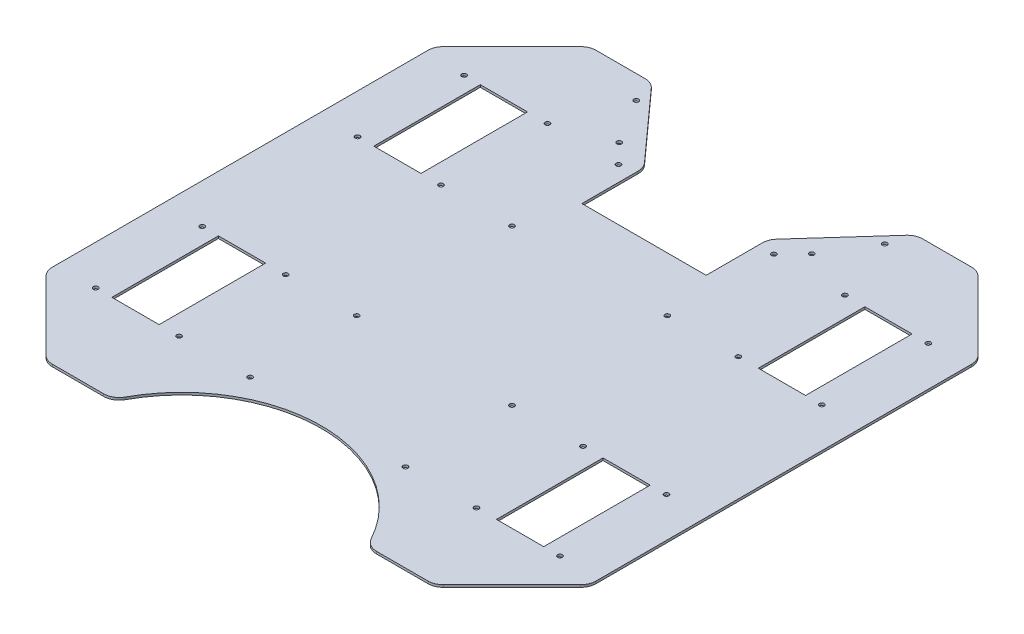
SolidWorks part; units mm, degrees
ref_plane "前视基准面" through (0, 0, 0) normal (0, 0, 1) x (1, 0, 0)
ref_plane "上视基准面" through (0, 0, 0) normal (0, 1, 0) x (1, 0, 0)
ref_plane "右视基准面" through (0, 0, 0) normal (1, 0, 0) x (0, 0, -1)
other "Configuration Table"
sketch "草图1" plane through (0, 0, 0) normal (0, 1, 0) x (1, 0, 0)
  line L0 (-125, 175) -> (-175, 125)
  line L1 (125, -175) -> (81.7103, -175)
  line L2 (175, -125) -> (175, 125)
  line L3 (125, 175) -> (85, 175)
  line L4 (-175, -125) -> (-175, 125)
  line L5 (-85, 175) -> (-40, 125)
  line L7 (125, 175) -> (175, 125)
  line L8 (175, -125) -> (125, -175)
  line L9 (-125, -175) -> (-175, -125)
  line L10 (40, 125) -> (85, 175)
  line L11 (-85, 175) -> (-125, 175)
  line L12 (40, 125) -> (40, 85)
  line L13 (40, 85) -> (-40, 85)
  line L14 (-40, 85) -> (-40, 125)
  line L15 (-138.994, 50) -> (-108.594, 50)
  line L16 (-108.594, 50) -> (-108.594, 118.58)
  line L17 (-108.594, 118.58) -> (-138.994, 118.58)
  line L18 (-138.994, 118.58) -> (-138.994, 50)
  line L19 (108.594, 50) -> (138.994, 50)
  line L20 (138.994, 50) -> (138.994, 118.58)
  line L21 (138.994, 118.58) -> (108.594, 118.58)
  line L22 (108.594, 118.58) -> (108.594, 50)
  line L23 (-175, 0) -> (175, 0) construction
  line L24 (-108.594, -118.58) -> (-138.994, -118.58)
  line L25 (-108.594, -50) -> (-108.594, -118.58)
  line L26 (-138.994, -50) -> (-108.594, -50)
  line L27 (-138.994, -118.58) -> (-138.994, -50)
  line L28 (138.994, -118.58) -> (108.594, -118.58)
  line L29 (138.994, -50) -> (138.994, -118.58)
  line L30 (108.594, -50) -> (138.994, -50)
  line L31 (108.594, -118.58) -> (108.594, -50)
  line L32 (-81.7103, -175) -> (-125, -175)
  line L33 (-80, 160) -> (-62, 131) construction
  circle A0 centre (-62, 131) radius 1.55
  circle A1 centre (-80, 160) radius 1.55
  circle A2 centre (62, 131) radius 1.55
  circle A3 centre (80, 160) radius 1.55
  circle A4 centre (-50, 118.58) radius 1.55
  circle A5 centre (-50, 50) radius 1.55
  circle A6 centre (-95.72, 50) radius 1.55
  circle A7 centre (-95.72, 118.58) radius 1.55
  circle A12 centre (-149.434, 118.58) radius 1.55
  circle A13 centre (-149.434, 50) radius 1.55
  circle A14 centre (-50, -118.58) radius 1.55
  circle A15 centre (-50, -50) radius 1.55
  circle A16 centre (-95.72, -50) radius 1.55
  circle A17 centre (-95.72, -118.58) radius 1.55
  circle A18 centre (-149.434, -50) radius 1.55
  circle A19 centre (-149.434, -118.58) radius 1.55
  circle A20 centre (50, 50) radius 1.55
  circle A21 centre (95.72, 50) radius 1.55
  circle A22 centre (95.72, 118.58) radius 1.55
  circle A23 centre (50, 118.58) radius 1.55
  circle A24 centre (149.434, 118.58) radius 1.55
  circle A25 centre (149.434, 50) radius 1.55
  circle A26 centre (149.434, -118.58) radius 1.55
  circle A27 centre (149.434, -50) radius 1.55
  circle A28 centre (95.72, -50) radius 1.55
  circle A29 centre (95.72, -118.58) radius 1.55
  circle A30 centre (50, -118.58) radius 1.55
  circle A31 centre (50, -50) radius 1.55
  arc A32 (-81.7103, -175) -> (81.7103, -175) centre (0, -212.7283) cw
  point P0 (0, 0)
  point P1 (-85, 175)
  point P2 (85, 175)
  point P3 (40, 125)
  point P4 (-40, 125)
  point P6 (125, 175)
  point P8 (175, 125)
  point P10 (175, -125)
  point P11 (125, -175)
  point P12 (-125, -175)
  point P13 (-175, -125)
  point P24 (-80, 160)
  point P25 (-62, 131)
  point P26 (62, 131)
  point P27 (80, 160)
  point P36 (-149.434, 118.58)
  point P37 (-149.434, 50)
  point P38 (-138.994, 118.58)
  point P39 (-108.594, 50)
  point P40 (-95.72, 118.58)
  point P41 (-95.72, 50)
  point P42 (-50, 118.58)
  point P43 (-50, 50)
  point P47 (-108.594, 118.58)
  point P53 (-138.994, 50)
  point P66 (-40, 85)
  point P67 (40, 85)
  point P70 (95.72, 50)
  point P71 (50, 50)
  point P72 (108.594, 50)
  point P73 (138.994, 50)
  point P74 (149.434, 50)
  point P75 (50, 118.58)
  point P76 (95.72, 118.58)
  point P77 (108.594, 118.58)
  point P78 (138.994, 118.58)
  point P81 (149.434, 118.58)
  point P85 (-50, -118.58)
  point P88 (-50, -50)
  point P91 (-95.72, -50)
  point P94 (-95.72, -118.58)
  point P101 (-149.434, -50)
  point P104 (-149.434, -118.58)
  point P118 (149.434, -118.58)
  point P121 (149.434, -50)
  point P128 (95.72, -50)
  point P131 (95.72, -118.58)
  point P134 (50, -118.58)
  point P137 (50, -50)
  dimension "D29" = 3.1
  dimension "D30" = 3.1
  dimension "D31" = 3.1
  dimension "D32" = 3.1
  dimension "D40" = 3.1
  dimension "D41" = 3.1
  dimension "D42" = 3.1
  dimension "D43" = 3.1
  dimension "D44" = 3.1
  dimension "D45" = 3.1
  dimension "D46" = 3.1
  dimension "D47" = 3.1
  dimension "D48" = 3.1
  dimension "D49" = 3.1
  dimension "D60" = 3.1
  dimension "D61" = 3.1
  dimension "D62" = 43.2897
  dimension "D63" = 90
  dimension "D1" = 175
  dimension "D2" = 175
  dimension "D3" = 125
  dimension "D4" = 125
  dimension "D5" = 125
  dimension "D6" = 125
  dimension "D7" = 125
  dimension "D8" = 125
  dimension "D9" = 125
  dimension "D10" = 125
  dimension "D11" = 175
  dimension "D12" = 175
  dimension "D13" = 40
  dimension "D14" = 40
  dimension "D15" = 85
  dimension "D16" = 85
  dimension "D17" = 125
  dimension "D18" = 125
  dimension "D19" = 40
  dimension "D20" = 45
  dimension "D21" = 160
  dimension "D22" = 160
  dimension "D23" = 80
  dimension "D24" = 80
  dimension "D25" = 62
  dimension "D26" = 131
  dimension "D27" = 62
  dimension "D28" = 131
  dimension "D33" = 50
  dimension "D34" = 118.58
  dimension "D35" = 50
  dimension "D36" = 45.72
  dimension "D37" = 12.874
  dimension "D38" = 30.4
  dimension "D39" = 10.44
  dimension "D50" = 40
  dimension "D51" = 40
  dimension "D52" = 85
  dimension "D53" = 85
  dimension "D54" = 138.013
  dimension "D55" = 50
  dimension "D56" = 45.72
  dimension "D57" = 12.874
  dimension "D58" = 30.4
  dimension "D59" = 10.44
  dimension "D64" = 0
extrude "凸台-拉伸1" add sketch "草图1" along normal blind 1.5 contours A1 | A0 | L8 L1 A32 L32 L9 L4 L0 L11 L5 L14 L13 L12 L10 L3 L7 L2 | A5 | A3 | A2 | A4 | A7 | A12 | L16 L17 L18 L15 | A6 | L21 L22 L19 L20 | A13 | A16 | A17 | A14 | A15 | A18 | A19 | L25 L24 L27 L26 | A20 | A21 | A22 | A23 | A24 | A25 | A28 | A26 | A27 | L28 L31 L30 L29 | A30 | A31 | A29
fillet "圆角1" radius 10 1 edges at (-40, 0.75, -125)
fillet "圆角2" radius 10 1 edges at (40, 0.75, -125)
fillet "圆角3" radius 10 12 edges at (-85, 0.75, -175) (85, 0.75, -175) (125, 0.75, -175) (175, 0.75, -125) (175, 0.75, 125) (125, 0.75, 175) (81.7103, 0.75, 175) (-81.7103, 0.75, 175) (-125, 0.75, 175) (-175, 0.75, 125) (-175, 0.75, -125) (-125, 0.75, -175)
